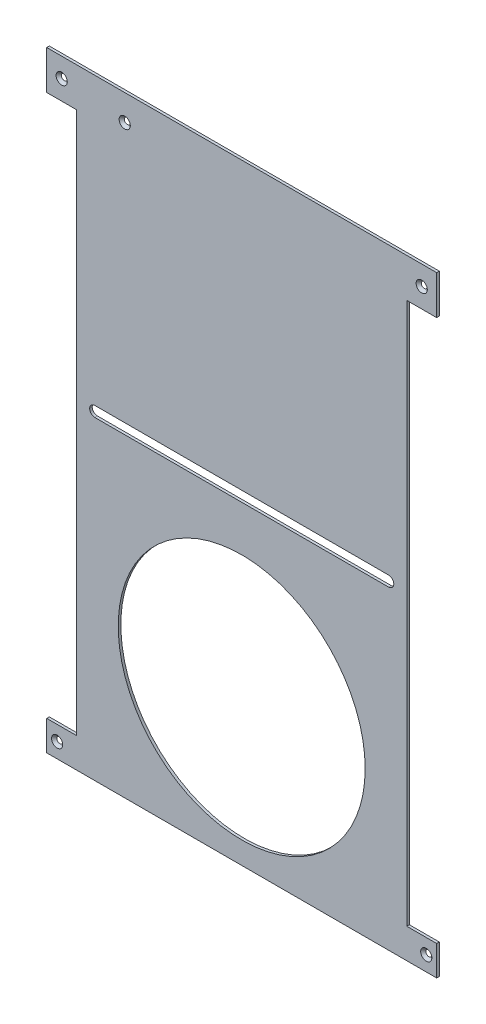
SolidWorks part; units mm, degrees
ref_plane "Ebene vorne" through (0, 0, 0) normal (0, 0, 1) x (1, 0, 0)
ref_plane "Ebene oben" through (0, 0, 0) normal (0, 1, 0) x (1, 0, 0)
ref_plane "Ebene rechts" through (0, 0, 0) normal (1, 0, 0) x (0, 0, -1)
sketch "Skizze1" plane through (0, 0, 0) normal (0, 0, 1) x (1, 0, 0)
  line L0 (0, 0) -> (300, 0)
  line L1 (300, 0) -> (300, 23)
  line L2 (300, 23) -> (277, 23)
  line L3 (277, 23) -> (277, 440)
  line L4 (277, 440) -> (300, 440)
  line L5 (300, 440) -> (300, 470)
  line L11 (0, 470) -> (0, 440)
  line L12 (0, 440) -> (23, 440)
  line L13 (23, 440) -> (23, 23)
  line L14 (23, 23) -> (0, 23)
  line L15 (0, 0) -> (0, 23)
  line L16 (0, 470) -> (300, 470)
  dimension "D1" = 23
  dimension "D2" = 23
  dimension "D3" = 30
  dimension "D4" = 23
  dimension "D5" = 30
  dimension "D6" = 300
  dimension "D7" = 470
  dimension "D9" = 23
  dimension "D10" = 23
  dimension "D12" = 23
extrude "Aufsatz-Linear austragen1" add sketch "Skizze1" along normal blind 2
hole_wizard "Formsenkung für M4 Senkschraube mit Innensechskant1" positions "Skizze2" profile "Skizze3" countersink size "M4" standard "DIN"
sketch "Skizze2" plane through (0, 0, 2) normal (0, 0, 1) x (1, 0, 0)
  line L4 (0, 0) -> (300, 0) construction
  line L6 (300, 0) -> (300, 23) construction
  line L7 (0, 23) -> (0, 0) construction
  line L8 (277, 23) -> (277, 440) construction
  line L9 (23, 440) -> (23, 23) construction
  line L10 (300, 470) -> (0, 470) construction
  point P0 (292, 11.5)
  point P2 (8, 11.5)
  point P39 (11.5, 455)
  point P41 (288.5, 455)
  dimension "D1" = 11.5
  dimension "D2" = 11.5
  dimension "D3" = 15
  dimension "D4" = 15
  dimension "D5" = 11.5
  dimension "D6" = 8
  dimension "D7" = 8
  dimension "D8" = 11.5
sketch "Skizze3" plane through (292, 11.5, 2) normal (1, 0, 0) x (0, -1, 0)
  line L0 (0, 0) -> (0, 16.3519)
  line L1 (0, 16.3519) -> (2.25, 15)
  line L2 (2.25, 15) -> (2.25, 2.05)
  line L3 (2.25, 2.05) -> (4.3, 0)
  line L5 (4.3, 0) -> (0, 0)
  line L6 (-2.25, 2.05) -> (-4.3, 0) construction
  line L10 (0, 16.3519) -> (-2.25, 15) construction
  line L11 (0, -6.35) -> (0, 107.95) construction
  dimension "Bohrerdurchmesser" = 4.5
  dimension "Bohrungstiefe" = 15
  dimension "Senkdurchmesser (Oben)" = 8.6
  dimension "Senkwinkel (Oben)" = 90
  dimension "Spitzenwinkel" = 118
sketch "Skizze4" plane through (0, 0, 2) normal (0, 0, 1) x (1, 0, 0)
  line L0 (0, 0) -> (300, 0) construction
  circle A0 centre (150, 112) radius 95
  dimension "D1" = 190
  dimension "D2" = 112
extrude "Schnitt-Linear austragen1" cut sketch "Skizze4" against normal blind 10
hole_wizard "Erdung" positions "Skizze5" profile "Skizze6" countersink size "M4" standard "DIN" end condition through all
sketch "Skizze5" plane through (0, 0, 2) normal (0, 0, 1) x (1, 0, 0)
  line L0 (0, 470) -> (0, 440) construction
  line L1 (0, 0) -> (300, 0) construction
  point P0 (60, 450)
  point P5 (0, 455)
  point P9 (23.4485, 651.6776)
  dimension "D1" = 60
  dimension "D2" = 450
sketch "Skizze6" plane through (60, 450, 2) normal (1, 0, 0) x (0, -1, 0)
  line L0 (0, 0) -> (0, 2)
  line L1 (0, 2) -> (2.25, 2)
  line L2 (2.25, 2) -> (2.25, 2.05)
  line L3 (2.25, 2.05) -> (4.3, 0)
  line L5 (4.3, 0) -> (0, 0)
  line L6 (-2.25, 2.05) -> (-4.3, 0) construction
  line L11 (0, -6.35) -> (0, 107.95) construction
  dimension "Bohrerdurchmesser" = 4.5
  dimension "Bohrungstiefe" = 2
  dimension "Senkdurchmesser (Oben)" = 8.6
  dimension "Senkwinkel (Oben)" = 90
sketch "Skizze7" plane through (0, 0, 0) normal (0, 0, -1) x (-1, 0, 0)
  line L0 (-277, 23) -> (-277, 440) construction
  line L1 (-267, 250) -> (-33, 250)
  line L2 (-267, 250) -> (-267, 242)
  line L3 (-267, 242) -> (-33, 242)
  line L4 (-33, 250) -> (-33, 242)
  line L5 (-23, 440) -> (-23, 23) construction
  line L6 (-300, 470) -> (0, 470) construction
  dimension "D1" = 10
  dimension "D2" = 10
  dimension "D3" = 8
  dimension "D4" = 220
extrude "Schnitt-Linear austragen2" cut sketch "Skizze7" against normal blind 10
fillet "Verrundung1" radius 4 4 edges at (33, 242, 1) (33, 250, 1) (267, 242, 1) (267, 250, 1)
